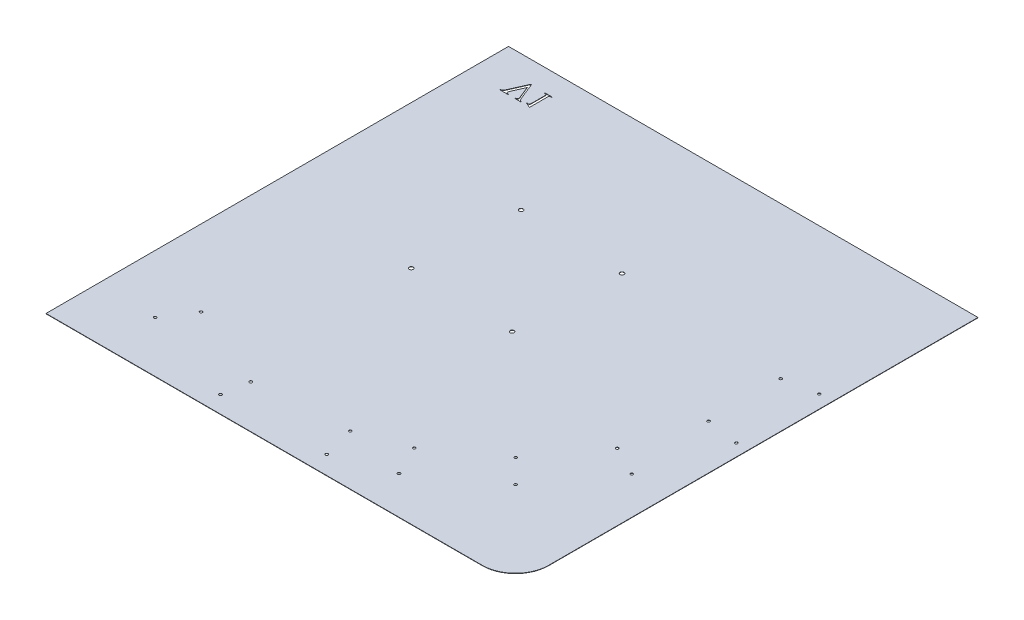
SolidWorks part; units mm, degrees
ref_plane "Спереди" through (0, 0, 0) normal (0, 0, 1) x (1, 0, 0)
ref_plane "Сверху" through (0, 0, 0) normal (0, 1, 0) x (1, 0, 0)
ref_plane "Справа" through (0, 0, 0) normal (1, 0, 0) x (0, 0, -1)
sketch "Эскиз1" plane through (0, 0, 0) normal (0, 1, 0) x (-1, 0, 0)
  line L1 (320.4611, -56.0282) -> (-387.6421, -56.0282)
  line L2 (320.4611, -56.0282) -> (320.4611, 641.6187)
  line L3 (320.4611, 641.6187) -> (-337.6421, 641.6187)
  line L4 (-387.6421, -56.0282) -> (-387.6421, 591.6187)
  circle A0 centre (232.9018, 564.4531) radius 2
  circle A1 centre (205.5747, 522.5761) radius 2
  circle A2 centre (76.7583, 576.5179) radius 2.1
  circle A3 centre (83.103, 616.0114) radius 2.1
  circle A4 centre (-62.4717, 565.6383) radius 2
  circle A5 centre (-75.307, 613.9675) radius 2
  circle A6 centre (-154.9052, 584.4983) radius 2
  circle A7 centre (-132.9253, 539.587) radius 2
  circle A8 centre (-257.2381, 511.0808) radius 2
  circle A9 centre (-221.9874, 475.6211) radius 2
  circle A10 centre (-331.0544, 409.5891) radius 2
  circle A11 centre (-286.4599, 386.9765) radius 2
  circle A12 centre (-319.8725, 282.5821) radius 2
  circle A13 centre (-369.3093, 290.0652) radius 2
  circle A14 centre (-367.9849, 163.6623) radius 2
  circle A15 centre (-318.823, 172.8034) radius 2
  circle A16 centre (-54.8341, 313.8264) radius 3
  circle A17 centre (104.1195, 307.0249) radius 3
  circle A18 centre (-61.6357, 154.8729) radius 3
  circle A19 centre (97.3179, 148.0713) radius 3
  arc A20 (-387.6421, 591.6187) -> (-337.6421, 641.6187) centre (-337.6421, 591.6187) cw
  dimension "D1" = 50
sheet metal parameters "Листовой металл1" thickness 0.5 parameters "D1"=3.3, "Толщина"=0.5
base flange "Базовая кромка1" sketch "Эскиз1" thickness 0.5 reverse thickness direction no parameters "D1"=3.3
sketch "Эскиз2" plane through (0, -0.5, 0) normal (0, -1, 0) x (1, 0, 0)
  text T0 "V1" font "Times New Roman" height 30
extrude "Вырез-Вытянуть1" cut sketch "Эскиз2" against normal blind 10 normal cut yes
flat pattern "Развертка1" [suppressed]
sketch "Сгиб-Линии1" plane through (0, 0, 0) normal (0, 1, 0) x (1, 0, 0)
sketch3d "Граничная рамка1" [suppressed]
  line L0 (658.1031, 647.6468, 0) -> (-50, 647.6468, 0) construction
  line L1 (658.1031, -50, 0) -> (-50, -50, 0) construction
  line L2 (658.1031, 647.6468, 0) -> (658.1031, -50, 0) construction
  line L3 (-50, 647.6468, 0) -> (-50, -50, 0) construction
